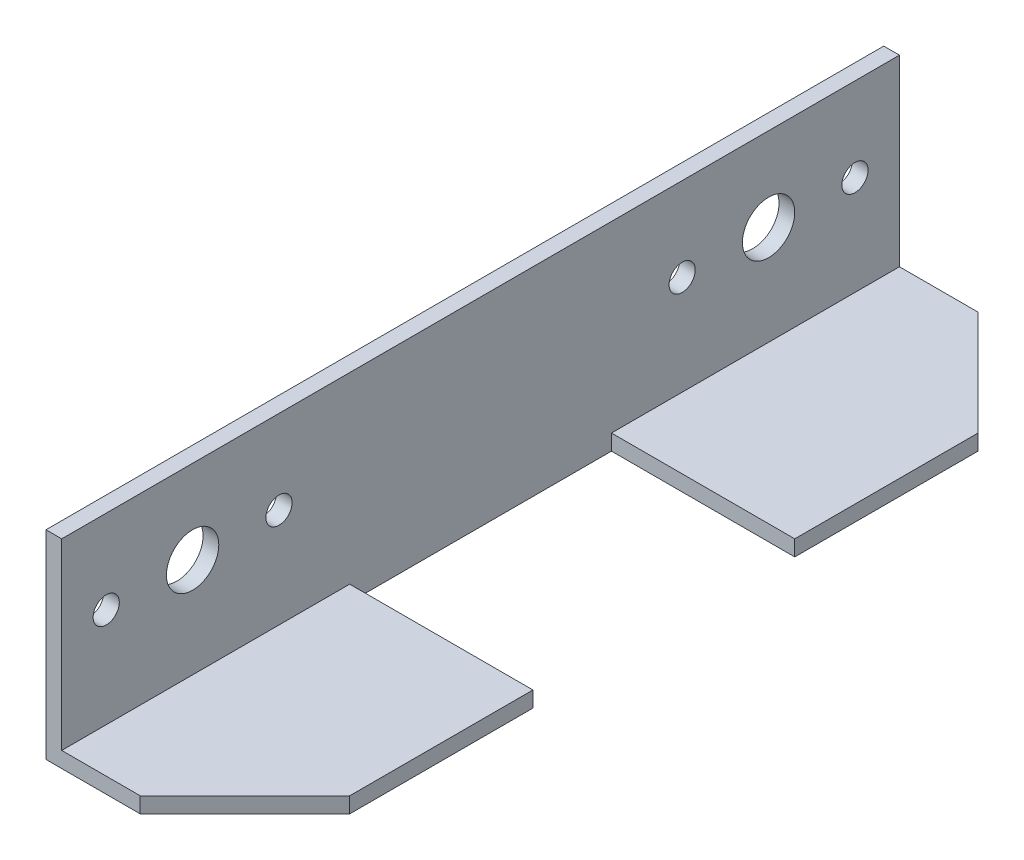
SolidWorks part; units mm, degrees
ref_plane "Alzado" through (0, 0, 0) normal (0, 0, 1) x (1, 0, 0)
ref_plane "Planta" through (0, 0, 0) normal (0, 1, 0) x (1, 0, 0)
ref_plane "Vista lateral" through (0, 0, 0) normal (1, 0, 0) x (0, 0, -1)
sketch "Croquis1" plane through (0, 0, 0) normal (0, 0, 1) x (1, 0, 0)
  line L0 (0, 0) -> (0, 38)
  line L1 (0, 0) -> (38, 0)
  line L2 (3, 3) -> (38, 3)
  line L3 (3, 3) -> (3, 38)
  line L4 (0, 38) -> (3, 38)
  line L5 (38, 3) -> (38, 0)
  dimension "D1" = 38
  dimension "D2" = 3
extrude "Saliente-Extruir1" add sketch "Croquis1" along normal blind 80 and the other way blind 80
sketch "Croquis2" plane through (0, 3, 0) normal (0, 1, 0) x (1, 0, 0)
  line L0 (3, 0) -> (38, 0) construction
  line L1 (3, 80) -> (3, -80) construction
  line L2 (38, 80) -> (38, -80) construction
  line L3 (3, 25) -> (3, -25)
  line L4 (3, -25) -> (38, -25)
  line L5 (38, -25) -> (38, 25)
  line L6 (3, 25) -> (38, 25)
  dimension "D1" = 25
extrude "Cortar-Extruir1" cut sketch "Croquis2" against normal up to surface (3 mm away) up to face at (19, 0, 0)
chamfer "Chaflán1" distance 20 angle 45 2 edges at (38, 1.5, -80) (38, 1.5, 80)
sketch "Croquis3" plane through (3, 0, 0) normal (1, 0, 0) x (0, 0, -1)
  line L0 (0, 0) -> (0, 38) construction
  line L1 (25, 0) -> (-25, 0) construction
  line L2 (80, 38) -> (-80, 38) construction
  line L3 (-80, 22) -> (0, 22) construction
  line L4 (-80, 3) -> (-80, 38) construction
  line L5 (-55, 38) -> (-55, 22) construction
  line L6 (-38.5, 22) -> (-71.5, 22) construction
  circle A0 centre (-55, 22) radius 5
  circle A1 centre (-71.5, 22) radius 2.5
  circle A2 centre (-38.5, 22) radius 2.5
  circle A3 centre (38.5, 22) radius 2.5
  circle A4 centre (55, 22) radius 5
  circle A5 centre (71.5, 22) radius 2.5
  point P16 (-55, 22)
  dimension "D4" = 10
  dimension "D5" = 5
  dimension "D1" = 16
  dimension "D2" = 55
  dimension "D3" = 33
extrude "Cortar-Extruir2" cut sketch "Croquis3" against normal up to surface (3 mm away) up to face at (0, 19, 0)
